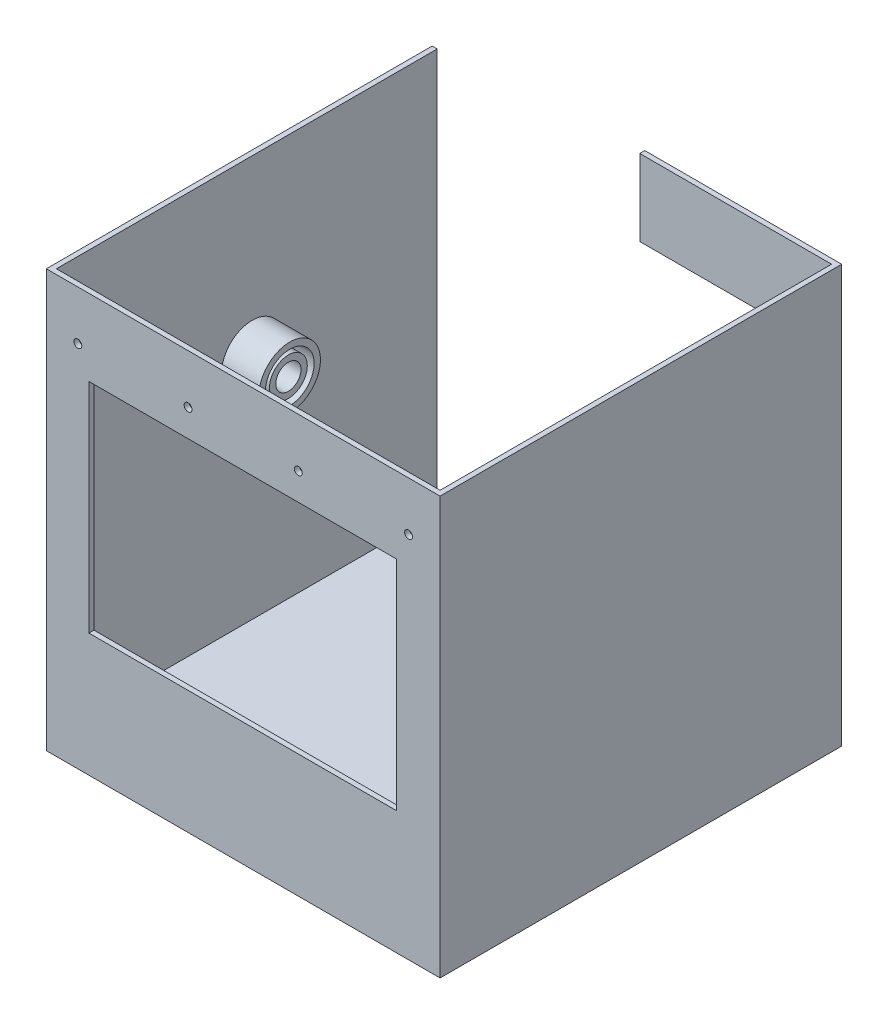
SolidWorks part; units mm, degrees
ref_plane "Front Plane" through (0, 0, 0) normal (0, 0, 1) x (1, 0, 0)
ref_plane "Top Plane" through (0, 0, 0) normal (0, 1, 0) x (1, 0, 0)
ref_plane "Right Plane" through (0, 0, 0) normal (1, 0, 0) x (0, 0, -1)
sketch "Sketch1" plane through (0, 0, 0) normal (0, 1, 0) x (1, 0, 0)
  line L1 (0, 0) -> (250, 0)
  line L2 (0, 0) -> (0, 255)
  line L3 (0, 255) -> (250, 255)
  line L4 (250, 0) -> (250, 255)
  dimension "D1" = 250
  dimension "D2" = 255
extrude "Boss-Extrude1" add sketch "Sketch1" along normal blind 10
sketch "Sketch2" plane through (0, 10, 0) normal (0, 1, 0) x (1, 0, 0)
  line L0 (3.2, 251.8) -> (3.2, 3.2)
  line L1 (0, 255) -> (250, 255)
  line L2 (0, 255) -> (0, 0)
  line L3 (0, 0) -> (250, 0)
  line L4 (250, 255) -> (250, 0)
  line L5 (3.2, 3.2) -> (246.8, 3.2)
  line L6 (246.8, 251.8) -> (246.8, 3.2)
  line L7 (3.2, 251.8) -> (246.8, 251.8)
  dimension "D1" = 3.2
extrude "Boss-Extrude2" add sketch "Sketch2" along normal blind 255
sketch "Sketch7" plane through (246.8, 0, 0) normal (-1, 0, 0) x (0, 0, 1)
  line L1 (-255, 265) -> (-255, 0) construction
  line L2 (0, 265) -> (0, 0) construction
  line L3 (-255, 265) -> (0, 265) construction
  circle A0 centre (-127.5, 155) radius 12
  circle A1 centre (-127.5, 155) radius 8
  dimension "D1" = 24
  dimension "D2" = 110
  dimension "D3" = 255
  dimension "D4" = 127.5
  dimension "D5" = 4
extrude "Boss-Extrude3" add sketch "Sketch7" along normal blind 23
sketch "Sketch10" plane through (246.8, 0, 0) normal (-1, 0, 0) x (0, 0, 1)
  circle A0 centre (-127.5, 155) radius 15.5
  circle A1 centre (-127.5, 155) radius 19.5
  dimension "D1" = 31
  dimension "D2" = 4
extrude "Boss-Extrude4" add sketch "Sketch10" along normal blind 31
sketch "Sketch11" plane through (3.2, 0, 0) normal (1, 0, 0) x (0, 0, -1)
  line L1 (251.8, 265) -> (3.2, 265) construction
  line L3 (255, 265) -> (255, 0) construction
  line L5 (0, 265) -> (0, 0) construction
  circle A0 centre (127.5, 155) radius 19.5
  circle A4 centre (127.5, 155) radius 15.5
  dimension "D1" = 39
  dimension "D3" = 127.5
  dimension "D4" = 110
  dimension "D5" = 127.5
  dimension "D2" = 4
extrude "Boss-Extrude5" add sketch "Sketch11" along normal blind 31
sketch "Sketch12" plane through (3.2, 0, 0) normal (1, 0, 0) x (0, 0, -1)
  circle A0 centre (127.5, 155) radius 12
  circle A1 centre (127.5, 155) radius 8
  dimension "D1" = 24
  dimension "D2" = 4
extrude "Boss-Extrude6" add sketch "Sketch12" along normal blind 23
sketch "Sketch14" plane through (0, 0, 0) normal (0, 0, 1) x (1, 0, 0)
  line L0 (0, 265) -> (0, 0) construction
  circle A0 centre (160, 233.8333) radius 2.5
  circle A1 centre (90, 233.8333) radius 2.5
  circle A2 centre (20, 233.8333) radius 2.5
  circle A3 centre (230, 233.8333) radius 2.5
  dimension "D1" = 5
  dimension "D2" = 20
  dimension "D3" = 70
  dimension "D4" = 70
  dimension "D5" = 70
extrude "Cut-Extrude3" cut sketch "Sketch14" against normal blind 23
sketch "Sketch16" plane through (0, 0, 0) normal (0, 0, 1) x (1, 0, 0)
  line L1 (27.0397, 216.5722) -> (222.4643, 216.5722)
  line L2 (27.0397, 216.5722) -> (27.0397, 78.1879)
  line L3 (27.0397, 78.1879) -> (222.4643, 78.1879)
  line L4 (222.4643, 216.5722) -> (222.4643, 78.1879)
extrude "Cut-Extrude4" cut sketch "Sketch16" against normal through all both and the other way through all
sketch "Sketch19" plane through (0, 0, -255) normal (0, 0, -1) x (-1, 0, 0)
  line L0 (-125, 265) -> (-125, 0)
  line L1 (-250, 265) -> (0, 265) construction
  line L2 (-250, 0) -> (0, 0) construction
extrude "Cut-Extrude5" cut sketch "Sketch19" against normal blind 10 and the other way through all
